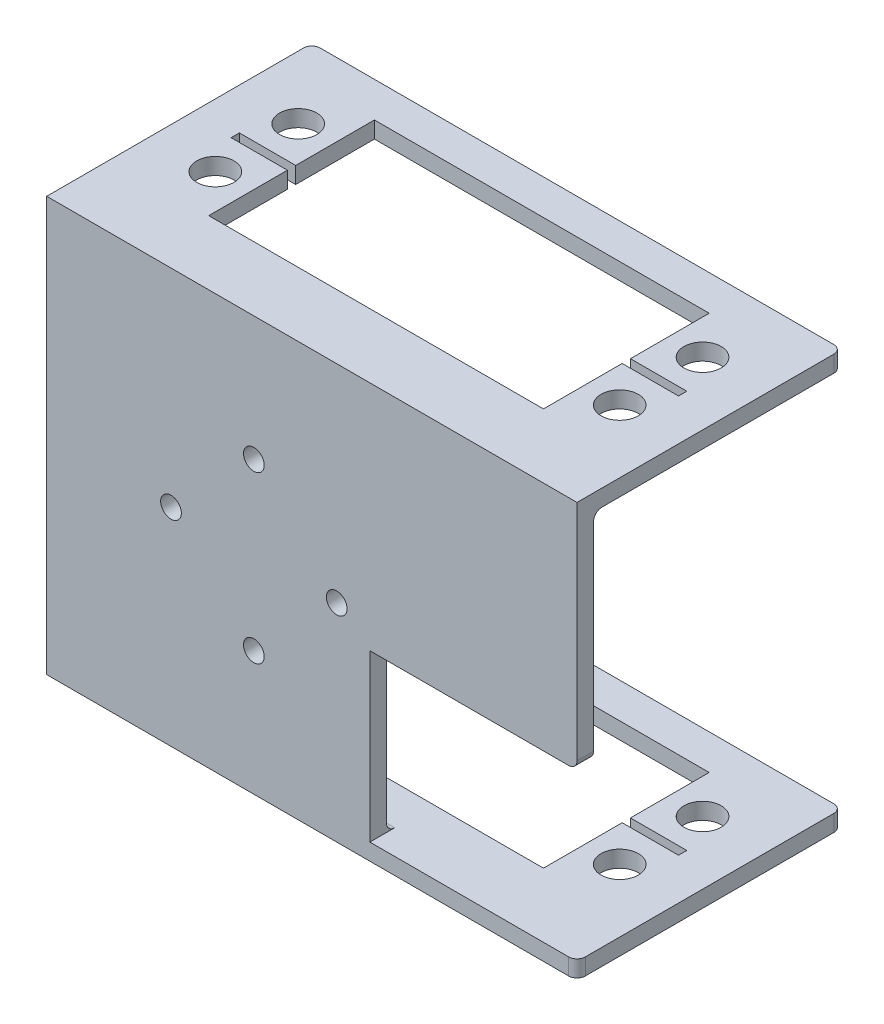
SolidWorks part; units mm, degrees
ref_plane "Front Plane" through (0, 0, 0) normal (0, 0, 1) x (1, 0, 0)
ref_plane "Top Plane" through (0, 0, 0) normal (0, 1, 0) x (1, 0, 0)
ref_plane "Right Plane" through (0, 0, 0) normal (1, 0, 0) x (0, 0, -1)
sketch "Sketch1" plane through (0, 0, 0) normal (0, 1, 0) x (1, 0, 0)
  line L1 (0, 0) -> (100, 0)
  line L2 (0, 0) -> (0, 32)
  line L3 (0, 32) -> (100, 32)
  line L4 (100, 0) -> (100, 32)
  dimension "D1" = 100
  dimension "D2" = 32
extrude "Boss-Extrude1" add sketch "Sketch1" along normal blind 2
sketch "Sketch2" plane through (0, 0, 0) normal (0, -1, 0) x (1, 0, 0)
  line L0 (0, -32) -> (0, 0) construction
  line L1 (100, 0) -> (0, 0)
  line L2 (100, 0) -> (100, -2)
  line L3 (100, -2) -> (0, -2)
  line L4 (0, 0) -> (0, -2)
  dimension "D1" = 2
extrude "Boss-Extrude2" add sketch "Sketch2" along normal blind 46
sketch "Sketch3" plane through (0, 0, 0) normal (0, 0, 1) x (1, 0, 0)
  line L1 (100, -46) -> (0, -46)
  line L2 (100, -46) -> (100, -48)
  line L3 (100, -48) -> (0, -48)
  line L4 (0, -46) -> (0, -48)
  dimension "D1" = 2
extrude "Boss-Extrude3" add sketch "Sketch3" against normal blind 32
sketch "Sketch4" plane through (0, 2, 0) normal (0, 1, 0) x (1, 0, 0)
  line L0 (0, 32) -> (0, 22.75)
  line L1 (0, 32) -> (0, 0) construction
  line L2 (0, 22.75) -> (7.6, 22.75)
  line L3 (7.6, 22.75) -> (7.6, 12.75)
  line L4 (7.6, 22.75) -> (11.8, 22.75)
  line L5 (11.8, 22.75) -> (11.8, 27.75)
  line L6 (7.6, 12.75) -> (11.8, 12.75)
  line L7 (11.8, 12.75) -> (11.8, 7.75)
  line L8 (11.8, 7.75) -> (11.8, 22.75)
  line L9 (11.8, 27.75) -> (52.2, 27.75)
  line L10 (52.2, 27.75) -> (52.2, 7.75)
  line L11 (52.2, 7.75) -> (11.8, 7.75)
  line L12 (7.6, 22.75) -> (56.4, 22.75)
  line L13 (7.6, 12.75) -> (56.4, 12.75)
  line L14 (7.6, 22.75) -> (7.6, 18.25)
  line L15 (11.8, 18.25) -> (5, 18.25)
  line L16 (5, 18.25) -> (5, 17.25)
  line L17 (5, 17.25) -> (11.8, 17.25)
  line L18 (52.2, 18.25) -> (59, 18.25)
  line L19 (52.2, 17.25) -> (59, 17.25)
  line L20 (59, 18.25) -> (59, 17.25)
  circle A0 centre (7.6, 22.75) radius 2.25
  circle A1 centre (7.6, 12.75) radius 2.25
  circle A2 centre (56.4, 12.75) radius 2.25
  circle A3 centre (56.4, 22.75) radius 2.25
  dimension "D1" = 4.2
  dimension "D2" = 6.8
  dimension "D3" = 6.8
  dimension "D4" = 6.8
extrude "Cut-Extrude1" cut sketch "Sketch4" against normal through all both and the other way through all contours L3 A0 L4 | L2 A0 L3 | L4 A0 L2 | L3 A1 L6 | L6 A1 L3 | L8 L13 L10 L12 | L5 L12 L10 L9 | L13 L7 L11 L10 | A2 | A3 | L16 L17 L3 L15 | L3 L17 L8 L15 | L20 L18 L10 L19 region at (7.6, 2, -23.7049) region at (56.4, 2, -24.9364) region at (56.4, 2, -14.9364) region at (6.6451, 2, -21.7951) region at (8.5549, 2, -21.7951) region at (32, 2, -17.75) region at (32, 2, -25.25) region at (9.7, 2, -17.75) region at (6.3, 2, -17.75) region at (55.6, 2, -17.75) region at (8.5549, 2, -13.7049) region at (7.2817, 2, -12.4317) region at (32, 2, -10.25)
sketch "Sketch5" plane through (0, -48, 0) normal (0, -1, 0) x (1, 0, 0)
  line L0 (59, -17.75) -> (64, -17.75)
  line L1 (59, -18.25) -> (59, -17.25) construction
  line L3 (0, -32) -> (100, -32) construction
  line L4 (64, -32) -> (64, 0)
  line L5 (0, 0) -> (100, 0) construction
  line L7 (64, 0) -> (100, 0)
  line L9 (64, -32) -> (100, -32)
  line L10 (100, 0) -> (100, -32)
  line M5 (100, 0) -> (0, 0)
  line M7 (0, -32) -> (100, -32)
  line M8 (100, -32) -> (100, 0)
extrude "Cut-Extrude2" cut sketch "Sketch5" against normal through all both and the other way through all contours L4 M7 M8 M5 region at (82, -48, -16)
sketch "Sketch6" plane through (0, 0, -2) normal (0, 0, -1) x (-1, 0, 0)
  line L1 (-64, -46) -> (-39, -46)
  line L2 (-64, -46) -> (-64, -26)
  line L3 (-64, -26) -> (-39, -26)
  line L4 (-39, -46) -> (-39, -26)
  dimension "D1" = 25
  dimension "D2" = 20
extrude "Cut-Extrude3" cut sketch "Sketch6" against normal blind 2
fillet "Fillet1" radius 1 8 edges at (0, 1, -32) (0, -47, -32) (64, -47, -32) (64, 1, -32) (32, 0, -2) (19.5, -46, -2) (64, -47, 0) (64, -26, -1)
sketch "Sketch7" plane through (0, 0, -2) normal (0, 0, -1) x (-1, 0, 0)
  line L0 (0, -46) -> (-39, -46) construction
  line L2 (0, -45) -> (0, -1) construction
  circle A0 centre (-25, -23) radius 10
  circle A1 centre (-25, -13) radius 1.5
  circle A2 centre (-15, -23) radius 1.5
  circle A3 centre (-25, -33) radius 1.5
  circle A4 centre (-35, -23) radius 1.5
  point P17 (-25, -23)
  dimension "D1" = 20
  dimension "D3" = 25
  dimension "D4" = 4
  dimension "D2" = 23
hole_wizard "M3 Tapped Hole1" positions "3DSketch1" profile "Sketch8" tap size "M3" standard "ISO" end condition through all
sketch3d "3DSketch1"
  point P0 (25, -13, -2)
  point P3 (35, -23, -2)
  point P6 (25, -33, -2)
  point P9 (15, -23, -2)
sketch "Sketch8" plane through (25, -13, -2) normal (1, 0, 0) x (0, 1, 0)
  line L0 (0, 0) -> (0, 2)
  line L1 (0, 2) -> (1.25, 2)
  line L2 (1.25, 2) -> (1.25, 0)
  line L5 (1.25, 0) -> (0, 0)
  line L11 (0, -6.35) -> (0, 107.95) construction
  dimension "Thru Tap Drill Dia." = 2.5
  dimension "Thru Tap Drill Depth" = 2
cosmetic thread "Hole Thread1" parameters "D2"=3
cosmetic thread "Hole Thread2" parameters "D2"=3
cosmetic thread "Hole Thread3" parameters "D2"=3
cosmetic thread "Hole Thread4" parameters "D2"=3
